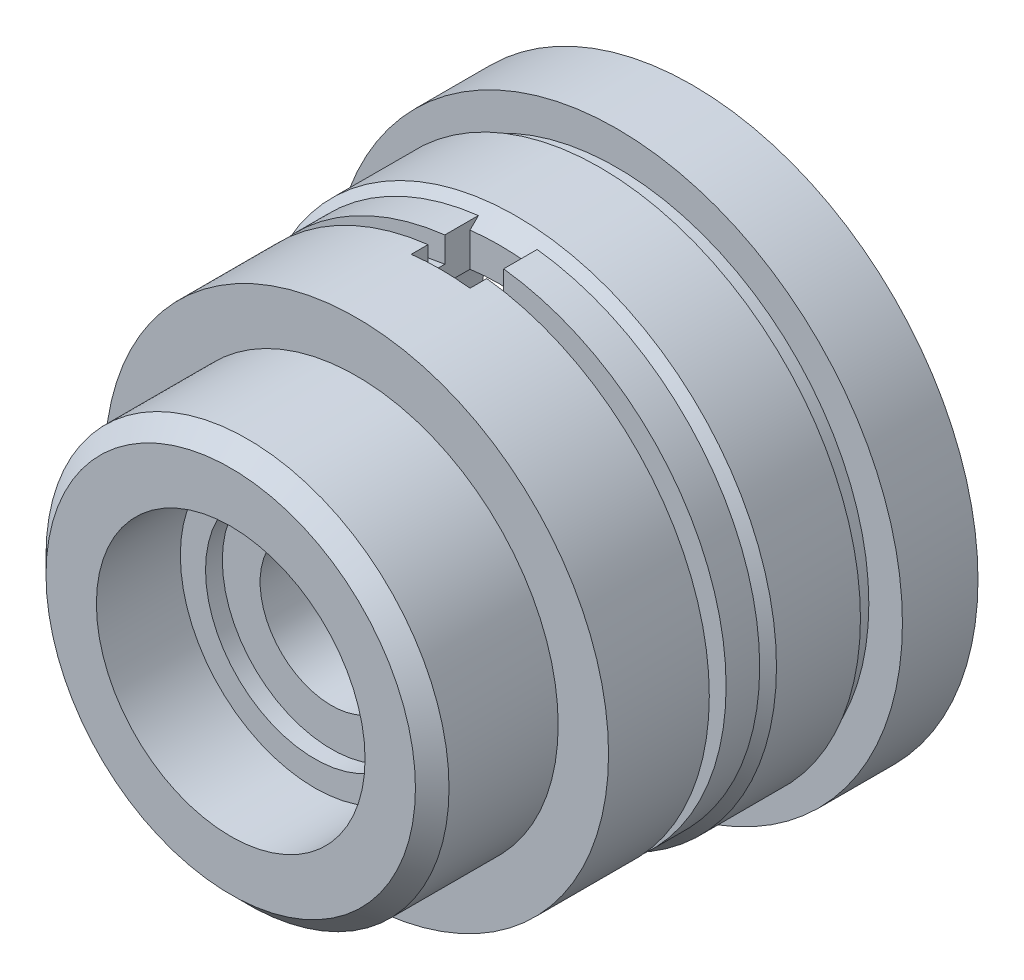
SolidWorks part; units mm, degrees
material "Zinc AC41A Alloy, As Cast"
ref_plane "Plan de face" through (0, 0, 0) normal (0, 0, 1) x (1, 0, 0)
ref_plane "Plan de dessus" through (0, 0, 0) normal (0, 1, 0) x (1, 0, 0)
ref_plane "Plan de droite" through (0, 0, 0) normal (1, 0, 0) x (0, 0, -1)
sketch "Sketch1" plane through (0, 0, 0) normal (0, 0, 1) x (1, 0, 0)
  circle A1 centre (0, 0) radius 17
  dimension "D2" = 34
extrude "Boss-Extrude1" add sketch "Sketch1" along normal blind 4.5
sketch "Sketch2" plane through (0, 0, 4.5) normal (0, 0, 1) x (1, 0, 0)
  circle A0 centre (0, 0) radius 15
  dimension "D1" = 30
extrude "Boss-Extrude2" add sketch "Sketch2" along normal blind 1
sketch "Sketch3" plane through (0, 0, 5.5) normal (0, 0, 1) x (1, 0, 0)
  circle A0 centre (0, 0) radius 15.5
  dimension "D1" = 31
extrude "Boss-Extrude3" add sketch "Sketch3" along normal blind 6
cosmetic thread "Cosmetic Thread1" parameters "D2"=30
sketch "Sketch7" plane through (0, 0, 11.5) normal (0, 0, 1) x (1, 0, 0)
  circle A1 centre (0, 0) radius 15
  dimension "D1" = 30
extrude "Boss-Extrude4" add sketch "Sketch7" along normal blind 8.5
sketch "Sketch8" plane through (0, 0, 20) normal (0, 0, 1) x (1, 0, 0)
  circle A0 centre (0, 0) radius 12
  dimension "D1" = 24
extrude "Boss-Extrude5" add sketch "Sketch8" along normal blind 7.5
sketch "Sketch9" plane through (0, 0, 0) normal (0, 1, 0) x (1, 0, 0)
  line L0 (-15, -11.5) -> (15, -11.5) construction
  line L1 (-1.75, -11.5) -> (1.75, -11.5)
  line L2 (-1.75, -11.5) -> (-1.75, -15)
  line L3 (-1.75, -15) -> (1.75, -15)
  line L4 (1.75, -11.5) -> (1.75, -15)
  line L5 (0, 0) -> (0, -15) construction
  line L6 (17, 0) -> (-17, 0) construction
  dimension "D1" = 3.5
  dimension "D2" = 3.5
  dimension "D3" = 3.5
  dimension "D4" = 1.75
extrude "Cut-Extrude1" cut sketch "Sketch9" against normal up to next and the other way up to next
chamfer "Chamfer1" distance 1 angle 45 1 edges at (15.5, 0, 11.5)
chamfer "Chamfer2" distance 1 angle 45 1 edges at (12, 0, 27.5)
sketch "Sketch10" plane through (0, 0, 0) normal (0, 0, -1) x (-1, 0, 0)
  circle A0 centre (0, 0) radius 12.5
  dimension "D1" = 25
extrude "Cut-Extrude2" cut sketch "Sketch10" against normal blind 18
sketch "Sketch11" plane through (0, 0, 27.5) normal (0, 0, 1) x (1, 0, 0)
  circle A0 centre (0, 0) radius 8
  dimension "D1" = 16
extrude "Cut-Extrude3" cut sketch "Sketch11" against normal blind 5
sketch "Sketch12" plane through (0, 0, 22.5) normal (0, 0, 1) x (1, 0, 0)
  circle A0 centre (0, 0) radius 6.5
  dimension "D1" = 13
extrude "Cut-Extrude4" cut sketch "Sketch12" against normal blind 1
sketch "Sketch13" plane through (0, 0, 21.5) normal (0, 0, 1) x (1, 0, 0)
  circle A0 centre (0, 0) radius 4.25
  dimension "D1" = 8.5
extrude "Cut-Extrude5" cut sketch "Sketch13" against normal blind 3.5 contours A0
sketch "Sketch6" plane through (0, 0, 0) normal (1, 0, 0) x (0, 0, -1)
  line L0 (0, 17) -> (0, 14.5) construction
  line L1 (0, -17) -> (0, 17) construction
  line L3 (0, 14.5) -> (0, 15.6)
  line L4 (0, 15.6) -> (-1.5609, 14.6719)
  line L9 (-1.6587, 14.5) -> (0, 14.5)
  arc A0 (-1.6587, 14.5) -> (-1.5609, 14.6719) centre (-1.4587, 14.5) cw
  dimension "D6" = 0.9281
  dimension "D1" = 2.5
  dimension "D2" = 1.5609
  dimension "D3" = 1.6587
  dimension "D4" = 1.1
revolve "Cut-Revolve4" cut sketch "Sketch6" angle 360 about L9
sketch "Sketch17" plane through (0, 0, 0) normal (1, 0, 0) x (0, 0, -1)
  line L0 (0, 0) -> (-14, 0) construction
  line L1 (-14, 0) -> (-14, 13.5) construction
  line L2 (-14, 13.5) -> (-14, 15)
  line L3 (-14, 15) -> (-13, 15)
  line L4 (-13, 15) -> (-13, 13.5)
  line L5 (-13, 13.5) -> (-14, 13.5)
  dimension "D1" = 14
  dimension "D2" = 13.5
  dimension "D3" = 1.5
  dimension "D4" = 1
revolve "Cut-Revolve5" cut sketch "Sketch17" angle 360 about L0
sketch "Sketch22" plane through (0, 0, 18) normal (0, 0, -1) x (-1, 0, 0)
  line L0 (0, 0) -> (0, 8.5) construction
  line L2 (0, 0) -> (7.3612, -4.25) construction
  line L4 (-7.3612, -4.25) -> (0, 0) construction
  point P0 (0, 8.5)
  point P11 (7.3612, -4.25)
  point P12 (-7.3612, -4.25)
  dimension "D1" = 8.5
  dimension "D3" = 8.5
  dimension "D4" = 8.5
  dimension "D2" = 3
hole_wizard "Ø2.0 (2) Diameter Hole1" positions "Sketch22" profile "Sketch20" hole size "Ø2.0" standard "ANSI Metric"
sketch "Sketch20" plane through (0, 8.5, 18) normal (1, 0, 0) x (0, 1, 0)
  line L0 (0, 0) -> (0, 3.1009)
  line L1 (0, 3.1009) -> (1, 2.5)
  line L2 (1, 2.5) -> (1, 0)
  line L5 (1, 0) -> (0, 0)
  line L10 (0, 3.1009) -> (-1, 2.5) construction
  line L11 (0, -6.35) -> (0, 107.95) construction
  dimension "Hole Dia." = 2
  dimension "Hole Depth" = 2.5
  dimension "Drill Angle" = 118
